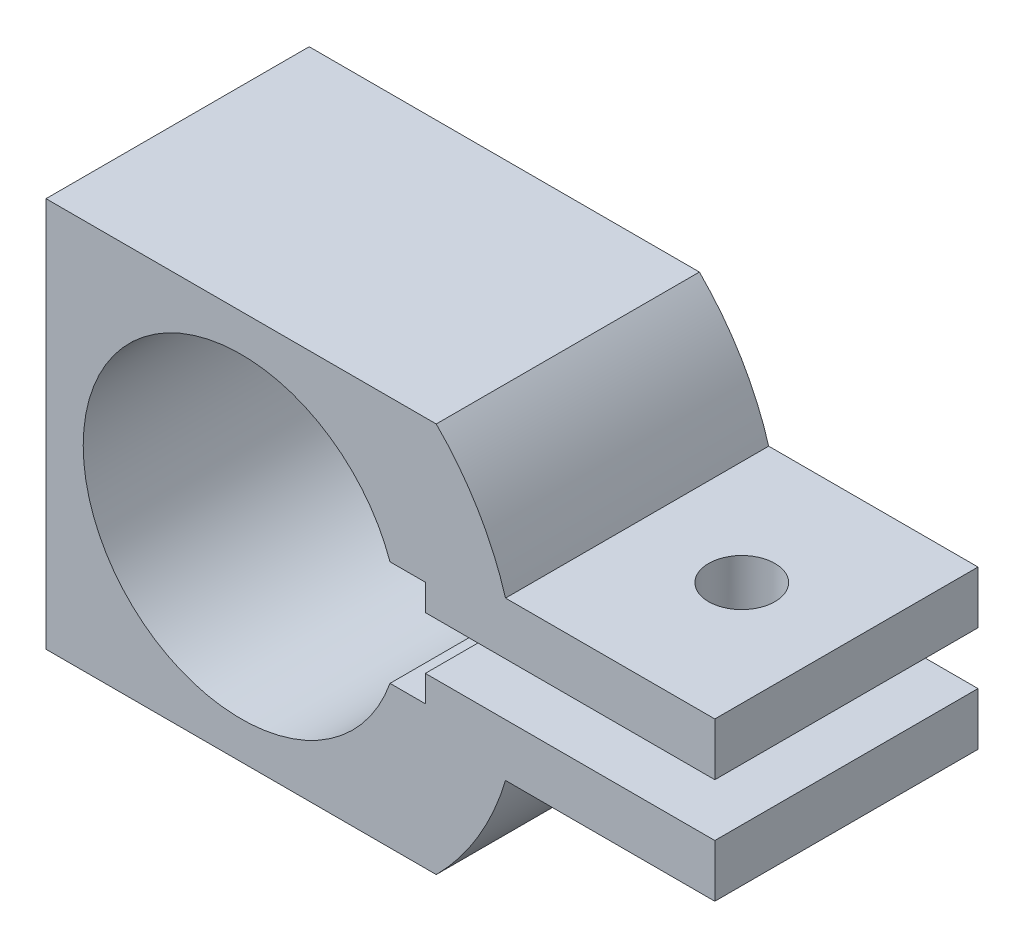
SolidWorks part; units mm, degrees
ref_plane "Front Plane" through (0, 0, 0) normal (0, 0, 1) x (1, 0, 0)
ref_plane "Top Plane" through (0, 0, 0) normal (0, 1, 0) x (1, 0, 0)
ref_plane "Right Plane" through (0, 0, 0) normal (1, 0, 0) x (0, 0, -1)
sketch "草图1" plane through (0, 0, 0) normal (0, 0, 1) x (1, 0, 0)
  line L0 (0, 0) -> (6, 0)
  line L1 (6, 0) -> (7, 0)
  line L3 (0, 0) -> (0, -2)
  line L5 (7, -2) -> (7, 0)
  line L6 (0, 0) -> (0, 6)
  line L8 (0, 2) -> (0, 0)
  line L9 (0, 0) -> (7, 0)
  line L10 (7, 2) -> (7, 0)
  line L11 (0, 0) -> (-6, 0)
  line L12 (-6, 6) -> (6, -6) construction
  line L13 (6, 6) -> (-6, -6) construction
  line L14 (-6, 6) -> (-7.4142, 7.4142) construction
  line L16 (-6, 6) -> (-6, -6)
  line L17 (-6, 6) -> (6, 6)
  line L18 (-6, 6) -> (-6, -6)
  line L19 (-6, -6) -> (6, -6)
  line L20 (6, 6) -> (6, -6)
  line L23 (-7.4142, 7.4142) -> (-7.4142, -7.4142) construction
  line L24 (0, 2) -> (6, 2)
  line L25 (-7.4142, 7.4142) -> (22.5858, 7.4142)
  line L26 (-7.4142, 7.4142) -> (-7.4142, -7.4142)
  line L27 (-7.4142, -7.4142) -> (22.5858, -7.4142)
  line L28 (22.5858, 7.4142) -> (22.5858, -7.4142)
  line L29 (6, 2) -> (6, -2)
  line L30 (6, -2) -> (0, -2)
  line L32 (6, 2) -> (7, 2)
  line L33 (6, 2) -> (6, -2)
  line L34 (6, -2) -> (7, -2)
  line L35 (7, 2) -> (7, -2)
  line L36 (0, 2) -> (6, 2)
  line L37 (0, 2) -> (0, -2)
  line L38 (0, -2) -> (6, -2)
  line L39 (6, 2) -> (6, -2)
  line L41 (6, 3) -> (6, -3)
  line L42 (6, 3) -> (18, 3)
  line L43 (6, 3) -> (6, -3)
  line L44 (6, -3) -> (18, -3)
  line L45 (18, 3) -> (18, -3)
  line L47 (7, 2) -> (7, -2)
  line L49 (18, 2) -> (18, -2)
  line L50 (18, -1) -> (7, -1)
  line L51 (18, -1) -> (18, 1)
  line L52 (18, 1) -> (7, 1)
  line L53 (7, -1) -> (7, 1)
  circle A0 centre (0, 0) radius 6
  circle A2 centre (0, 0) radius 10.4853
  point P20 (6, 2)
  point P21 (6, -2)
  point P22 (6, 3)
  point P25 (6, -3)
  point P30 (10.2928, 2)
  point P31 (10.2928, -2)
  point P32 (18, 1)
  point P33 (18, -1)
  point P34 (18, 1)
  point P41 (0, 0)
  dimension "D1" = 12
  dimension "D2" = 6
  dimension "D3" = 2
  dimension "D4" = 12
  dimension "D5" = 12
  dimension "D6" = 2
  dimension "D7" = 30
  dimension "D8" = 14.8284
  dimension "D9" = 6
extrude "凸台-拉伸2" add sketch "草图1" along normal blind 10 contours L25 L28 L27 L26
extrude "切除-拉伸9" cut sketch "草图1<11>" along normal blind 15 contours L11 A0 L3 region at (-0.7742, -2.9557, 0)
sketch "草图1<11>" plane through (0, 0, 0) normal (0, 0, 1) x (1, 0, 0) same geometry as "草图1"
extrude "切除-拉伸10" cut sketch "草图1<12>" along normal blind 30 contours L6 A0 L11 region at (-2.5465, 2.5465, 0)
sketch "草图1<12>" plane through (0, 0, 0) normal (0, 0, 1) x (1, 0, 0) same geometry as "草图1"
extrude "切除-拉伸11" cut sketch "草图1<13>" along normal blind 31 contours L0 A0 region at (2.9444, 0.9903, 0)
sketch "草图1<13>" plane through (0, 0, 0) normal (0, 0, 1) x (1, 0, 0) same geometry as "草图1"
extrude "切除-拉伸12" cut sketch "草图1<14>" along normal blind 40 contours A0 L0 L3 region at (2.9444, -0.9903, 0)
sketch "草图1<14>" plane through (0, 0, 0) normal (0, 0, 1) x (1, 0, 0) same geometry as "草图1"
extrude "切除-拉伸13" cut sketch "草图1<15>" along normal blind 17 contours A0 L6 region at (2.2626, 3.6569, 0)
sketch "草图1<15>" plane through (0, 0, 0) normal (0, 0, 1) x (1, 0, 0) same geometry as "草图1"
extrude "切除-拉伸17" cut sketch "草图1<19>" along normal blind 97 contours A0 L20 L36 | L32 L20 L1 L10 | L20 L34 L5 L1 | A0 L30 L20 region at (6.5, 1, 0) region at (5.8976, 1.5029, 0) region at (6.5, -1, 0) region at (5.8976, -1.5029, 0)
sketch "草图1<19>" plane through (0, 0, 0) normal (0, 0, 1) x (1, 0, 0) same geometry as "草图1"
extrude "切除-拉伸18" cut sketch "草图1<20>" along normal blind 285 contours A2 L49 L27 L28 L25 region at (9.1874, 5.4796, 0)
sketch "草图1<20>" plane through (0, 0, 0) normal (0, 0, 1) x (1, 0, 0) same geometry as "草图1"
extrude "切除-拉伸20" cut sketch "草图1<22>" along normal blind 202 contours A2 L50 L49 L52 region at (14.2347, 0, 0)
sketch "草图1<22>" plane through (0, 0, 0) normal (0, 0, 1) x (1, 0, 0) same geometry as "草图1"
sketch "草图2" plane through (0, -3, 0) normal (0, -1, 0) x (1, 0, 0)
  line L0 (10.0469, 10) -> (18, 0)
  line L1 (18, 0) -> (18, 10)
  line L2 (18, 10) -> (10.0469, 0)
  circle A0 centre (14.0235, 5) radius 1.26
  dimension "D1" = 2.52
extrude "切除-拉伸21" cut sketch "草图2" against normal blind 202 contours L0 A0 L2 | L2 A0 L0 | L0 A0 L2 | L2 A0 L0 region at (14.0235, -3, 5.7782) region at (13.2921, -3, 5) region at (14.7548, -3, 5) region at (14.0235, -3, 4.2218)
extrude "切除-拉伸22" cut sketch "草图1<23>" along normal blind 95 contours L50 A2 L52 L47 | A2 L50 L49 L52 region at (8.7347, 0, 0) region at (14.2347, 0, 0)
sketch "草图1<23>" plane through (0, 0, 0) normal (0, 0, 1) x (1, 0, 0) same geometry as "草图1"
